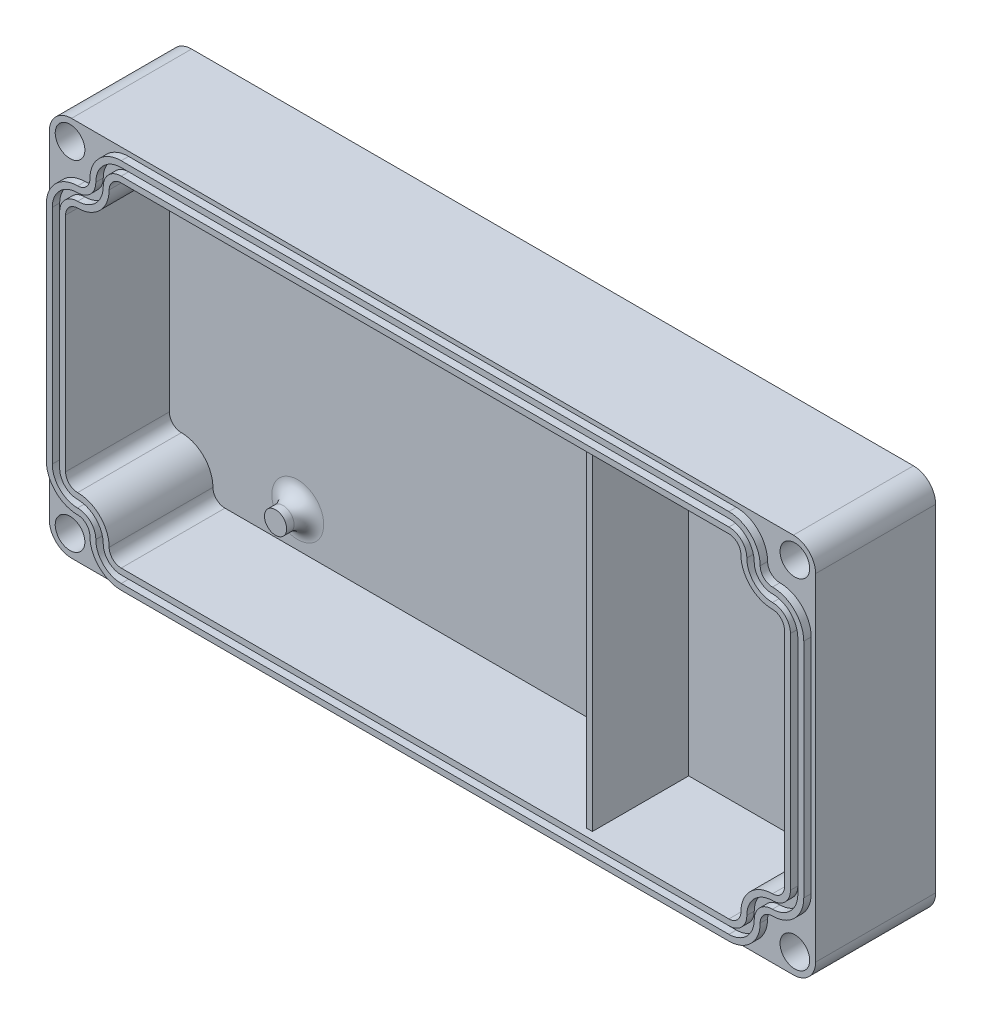
SolidWorks part; units mm, degrees
ref_plane "Plan de face" through (0, 0, 0) normal (0, 0, 1) x (1, 0, 0)
ref_plane "Plan de dessus" through (0, 0, 0) normal (0, 1, 0) x (1, 0, 0)
ref_plane "Plan de droite" through (0, 0, 0) normal (1, 0, 0) x (0, 0, -1)
sketch "Esquisse1" plane through (0, 0, 0) normal (0, 0, 1) x (1, 0, 0)
  line L1 (-48.5, 22.5) -> (48.5, 22.5)
  line L2 (-48.5, 22.5) -> (-48.5, -22.5)
  line L3 (-48.5, -22.5) -> (48.5, -22.5)
  line L4 (48.5, 22.5) -> (48.5, -22.5)
  line L5 (-48.5, 22.5) -> (48.5, -22.5) construction
  line L6 (-48.5, -22.5) -> (48.5, 22.5) construction
  point P0 (0, 0)
  dimension "D1" = 97
  dimension "D2" = 45
extrude "Boss.-Extru.1" add sketch "Esquisse1" along normal blind 13
shell "Coque1" thickness 3.2 removed face at (0, 0, 13) outward yes
ref_plane "Plan1" through (0, 0, 20) normal (0, 0, 1) x (1, 0, 0)
sketch "Esquisse8" plane through (0, 0, 20) normal (0, 0, 1) x (1, 0, 0)
  line L0 (21.5, 16.8946) -> (21.5, -12.3256)
  line L1 (48.5, -22.5) -> (48.5, 22.5) construction
  dimension "D1" = 27
sketch "Esquisse10" plane through (0, 0, 0) normal (0, 0, 1) x (1, 0, 0)
  line L0 (-48.5, 22.5) -> (-48.5, 15)
  line L1 (-48.5, 22.5) -> (-48.5, -22.5) construction
  line L2 (48.5, 22.5) -> (-48.5, 22.5) construction
  line L3 (-41, 22.5) -> (-48.5, 22.5)
  line L4 (-46.88, 15) -> (-48.5, 15) construction
  line L5 (-46.88, 15) -> (-46.88, 16.62) construction
  line L6 (-41, 20.88) -> (-42.62, 20.88) construction
  line L7 (-41, 20.88) -> (-41, 22.5) construction
  arc A1 (-48.5, 15) -> (-46.88, 16.62) centre (-46.88, 15) cw
  arc A2 (-46.88, 16.62) -> (-42.62, 20.88) centre (-46.88, 20.88) ccw
  arc A3 (-42.62, 20.88) -> (-41, 22.5) centre (-41, 20.88) cw
  dimension "D1" = 7.5
extrude "Boss.-Extru.2" add sketch "Esquisse10" along normal up to surface (13 mm away) up to face at (0, 0, 13)
mirror "Symétrie1" about plane through (0, 0, 0) normal (1, 0, 0) of "Boss.-Extru.2"
mirror "Symétrie2" about plane through (0, 0, 0) normal (0, 1, 0) of "Boss.-Extru.2"
mirror "Symétrie3" about plane through (0, 0, 0) normal (0, 1, 0) of "Symétrie1"
sketch "Esquisse13" plane through (0, 0, 13) normal (0, 0, 1) x (1, 0, 0)
  line L0 (-48.9, 22.9) -> (-48.9, 24.9) construction
  line L1 (51.7, 25.7) -> (-51.7, 25.7) construction
  line L2 (-48.9, 22.9) -> (-50.9, 22.9) construction
  line L4 (-51.7, 25.7) -> (-51.7, -25.7) construction
  circle A0 centre (-48.9, 22.9) radius 2
  circle A1 centre (-48.9, 22.9) radius 2.75 construction
  dimension "D1" = 4
  dimension "D4" = 5.5
  dimension "D2" = 0.8
  dimension "D3" = 0.8
extrude "Insert" cut sketch "Esquisse13" against normal blind 5.7
mirror "Symétrie4" about plane through (0, 0, 0) normal (1, 0, 0) of "Insert"
mirror "Symétrie5" about plane through (0, 0, 0) normal (0, 1, 0) of "Symétrie4"
sketch "Esquisse14" plane through (0, 0, 13) normal (0, 0, 1) x (1, 0, 0)
  line L0 (-41, 22.5) -> (41, 22.5)
  line L1 (48.5, 15) -> (48.5, -15)
  line L2 (41, -22.5) -> (-41, -22.5)
  line L3 (-48.5, -15) -> (-48.5, 15)
  line L4 (-50.3, -15) -> (-50.3, 15)
  line L5 (-41, 24.3) -> (41, 24.3)
  line L6 (50.3, 15) -> (50.3, -15)
  line L7 (41, -24.3) -> (-41, -24.3)
  arc A0 (41, 22.5) -> (42.62, 20.88) centre (41, 20.88) cw
  arc A1 (42.62, 20.88) -> (46.88, 16.62) centre (46.88, 20.88) ccw
  arc A2 (46.88, 16.62) -> (48.5, 15) centre (46.88, 15) cw
  arc A3 (48.5, -15) -> (46.88, -16.62) centre (46.88, -15) cw
  arc A4 (46.88, -16.62) -> (42.62, -20.88) centre (46.88, -20.88) ccw
  arc A5 (42.62, -20.88) -> (41, -22.5) centre (41, -20.88) cw
  arc A6 (-41, -22.5) -> (-42.62, -20.88) centre (-41, -20.88) cw
  arc A7 (-42.62, -20.88) -> (-46.88, -16.62) centre (-46.88, -20.88) ccw
  arc A8 (-46.88, -16.62) -> (-48.5, -15) centre (-46.88, -15) cw
  arc A9 (-48.5, 15) -> (-46.88, 16.62) centre (-46.88, 15) cw
  arc A10 (-46.88, 16.62) -> (-42.62, 20.88) centre (-46.88, 20.88) ccw
  arc A11 (-42.62, 20.88) -> (-41, 22.5) centre (-41, 20.88) cw
  arc A12 (-50.3, 15) -> (-46.88, 18.42) centre (-46.88, 15) cw
  arc A13 (-46.88, 18.42) -> (-44.42, 20.88) centre (-46.88, 20.88) ccw
  arc A14 (-44.42, 20.88) -> (-41, 24.3) centre (-41, 20.88) cw
  arc A15 (41, 24.3) -> (44.42, 20.88) centre (41, 20.88) cw
  arc A16 (44.42, 20.88) -> (46.88, 18.42) centre (46.88, 20.88) ccw
  arc A17 (46.88, 18.42) -> (50.3, 15) centre (46.88, 15) cw
  arc A18 (50.3, -15) -> (46.88, -18.42) centre (46.88, -15) cw
  arc A19 (46.88, -18.42) -> (44.42, -20.88) centre (46.88, -20.88) ccw
  arc A20 (44.42, -20.88) -> (41, -24.3) centre (41, -20.88) cw
  arc A21 (-41, -24.3) -> (-44.42, -20.88) centre (-41, -20.88) cw
  arc A22 (-44.42, -20.88) -> (-46.88, -18.42) centre (-46.88, -20.88) ccw
  arc A23 (-46.88, -18.42) -> (-50.3, -15) centre (-46.88, -15) cw
  dimension "D1" = 1.8
extrude "Extru.-Mince1" add sketch "Esquisse14" along normal blind 1 thin thin type one direction wall 0.8
fillet "Congé1" radius 3 4 edges at (-51.7, -25.7, 4.9) (51.7, -25.7, 4.9) (51.7, 25.7, 4.9) (-51.7, 25.7, 4.9)
sketch "Esquisse16" plane through (0, 0, 0) normal (0, 0, 1) x (1, 0, 0)
  circle A0 centre (-31.1716, 18.1378) radius 1.5
  circle A1 centre (14.1284, 18.1378) radius 1.5
  circle A2 centre (14.1284, -17.7622) radius 1.5
  circle A3 centre (-31.1716, -17.7622) radius 1.5
  point P0 (-31.1716, 18.1378)
  dimension "D1" = 3
  dimension "D2" = 3
  dimension "D3" = 3
  dimension "D4" = 3
extrude "Boss.-Extru.3" add sketch "Esquisse16" along normal blind 3
fillet "Congé2" radius 2 4 edges at (15.6284, -17.7622, 0) (15.6284, 18.1378, 0) (-29.6716, 18.1378, 0) (-29.6716, -17.7622, 0)
hole_wizard "Dégagement M1.61" positions "Esquisse20" profile "Esquisse19" hole size "M1.6" standard "Ansi Metric"
sketch "Esquisse20" plane through (0, 0, 3) normal (0, 0, 1) x (1, 0, 0)
  point P0 (14.1284, 18.1378)
  point P3 (14.1284, -17.7622)
  point P7 (-31.1716, 18.1378)
sketch "Esquisse19" plane through (14.1284, 18.1378, 3) normal (1, 0, 0) x (0, -1, 0)
  line L0 (0, 0) -> (0, 3.5408)
  line L1 (0, 3.5408) -> (0.9, 3)
  line L2 (0.9, 3) -> (0.9, 0)
  line L5 (0.9, 0) -> (0, 0)
  line L10 (0, 3.5408) -> (-0.9, 3) construction
  line L11 (0, -6.35) -> (0, 107.95) construction
  dimension "Diamètre du perçage" = 1.8
  dimension "Profondeur du perçage" = 3
  dimension "Angle de pointe" = 118
sketch "Esquisse17" plane through (0, 0, 13) normal (0, 0, 1) x (1, 0, 0)
  line L0 (21.5763, 9.753) -> (21.5763, -8.4958)
rib "Nervure19" sketch "Esquisse17" sketch "Esquisse17" thickness 0.8 extrusion direction normal to sketch draft on no parameters "D1"=0.8
equation "\"buse\"= 0.8"
equation "\"D1@Coque1\"=\"buse\"*4"
equation "\"hauteur\"=10"
equation "\"D1@Nervure1\"=\"hauteur\""
equation "\"D1@Nervure18\"=\"buse\""
equation "\"D2@Esquisse13\"=\"buse\"*1"
equation "\"D3@Esquisse13\"=1*\"buse\""
equation "\"D1@Esquisse14\"=\"buse\"*1+1"
